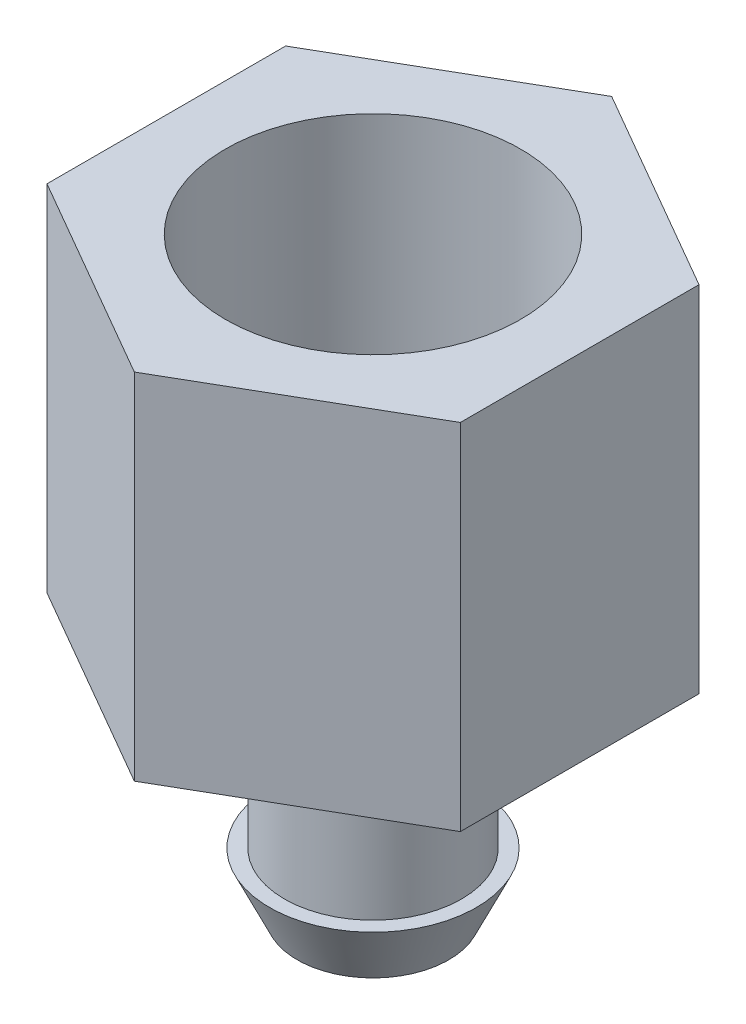
SolidWorks part; units mm, degrees
ref_plane "Plan de face" through (0, 0, 0) normal (0, 0, 1) x (1, 0, 0)
ref_plane "Plan de dessus" through (0, 0, 0) normal (0, 1, 0) x (1, 0, 0)
ref_plane "Plan de droite" through (0, 0, 0) normal (1, 0, 0) x (0, 0, -1)
sketch "Esquisse1" plane through (0, 0, 0) normal (0, 1, 0) x (1, 0, 0)
  line L0 (0, 0) -> (0, 8.0829) construction
  line L1 (0, 8.0829) -> (-7, 4.0415)
  line L2 (-7, 4.0415) -> (-7, -4.0415)
  line L3 (-7, -4.0415) -> (0, -8.0829)
  line L4 (0, -8.0829) -> (7, -4.0415)
  line L5 (7, -4.0415) -> (7, 4.0415)
  line L6 (7, 4.0415) -> (0, 8.0829)
  line L7 (0, 8.0829) -> (-0.0683, 7.9948) construction
  circle A0 centre (0, 0) radius 7 construction
  dimension "D1" = 14
extrude "Extrusion1" add sketch "Esquisse1" along normal blind 12
sketch "Esquisse2" plane through (0, 12, 0) normal (0, 1, 0) x (-1, 0, 0)
  circle A0 centre (0, 0) radius 5
  dimension "D1" = 10
extrude "Extrusion2" cut sketch "Esquisse2" against normal blind 10
sketch "Esquisse3" plane through (0, 0, 0) normal (0, -1, 0) x (1, 0, 0)
  circle A0 centre (0, 0) radius 3
  dimension "D1" = 6
extrude "Extrusion3" add sketch "Esquisse3" along normal blind 6
sketch "Esquisse5" plane through (0, -6, 0) normal (0, -1, 0) x (1, 0, 0)
  circle A0 centre (0, 0) radius 3.5
  dimension "D1" = 7
extrude "Extrusion5" add sketch "Esquisse5" along normal blind 2
sketch "Esquisse6" plane through (0, -8, 0) normal (0, -1, 0) x (1, 0, 0)
  circle A0 centre (0, 0) radius 1.75
  dimension "D1" = 3.5
extrude "Extrusion6" cut sketch "Esquisse6" against normal up to next
chamfer "Chanfrein2" distance 2 angle 25 1 edges at (0, -8, -3.5) first distance on face at (0, -8, -3.5)
